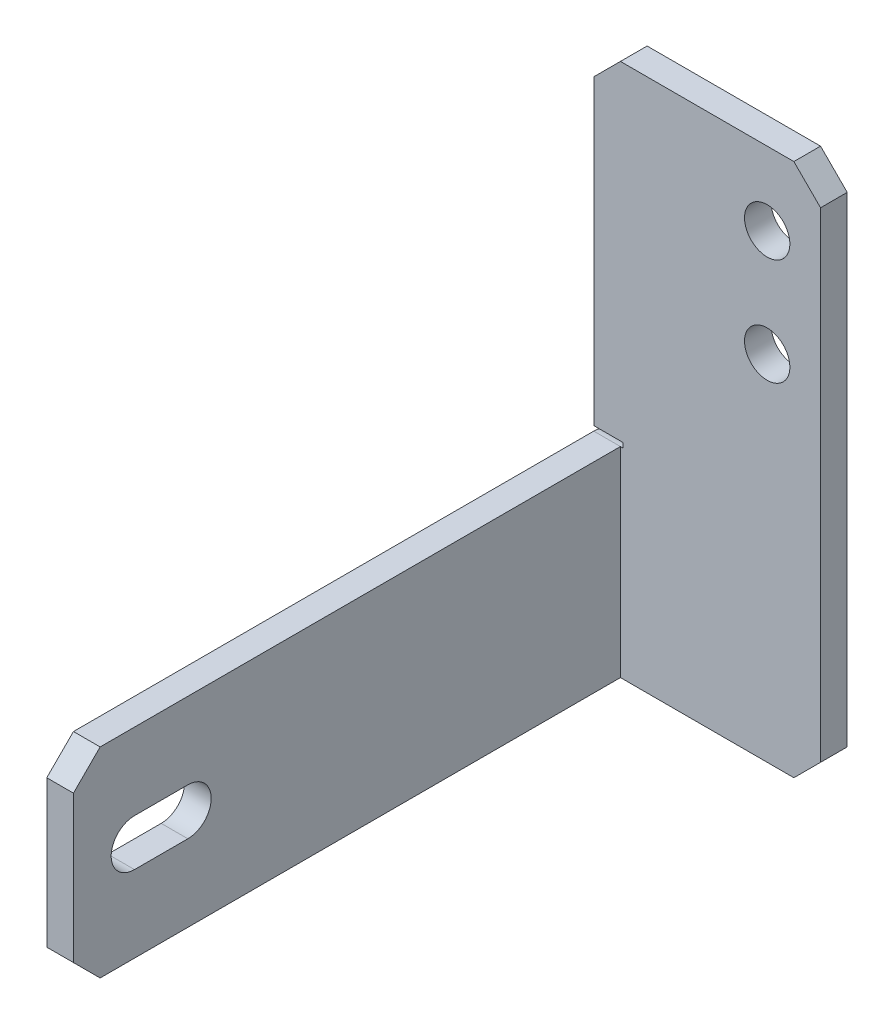
SolidWorks part; units mm, degrees
ref_plane "Front Plane" through (0, 0, 0) normal (0, 0, 1) x (1, 0, 0)
ref_plane "Top Plane" through (0, 0, 0) normal (0, 1, 0) x (1, 0, 0)
ref_plane "Right Plane" through (0, 0, 0) normal (1, 0, 0) x (0, 0, -1)
sketch "Sketch1" plane through (0, 0, 0) normal (0, 0, 1) x (1, 0, 0)
  line L0 (-8.0785, -9.7211) -> (-8.0785, -24.7211)
  line L1 (-8.0785, 15.2789) -> (8.9215, 15.2789)
  line L2 (-8.0785, 15.2789) -> (-8.0785, -9.3619)
  line L3 (-8.0785, -24.7211) -> (8.9215, -24.7211)
  line L4 (8.9215, 15.2789) -> (8.9215, -24.7211)
  line L5 (-8.0785, -9.3619) -> (-5.8785, -9.3619)
  line L7 (-8.0785, -9.7211) -> (-5.8785, -9.7211)
  line L8 (-5.8785, -9.3619) -> (-5.8785, -9.7211)
  circle A0 centre (4.9215, 9.7789) radius 1.7
  circle A1 centre (4.9215, 1.7789) radius 1.7
  dimension "D3" = 8
  dimension "D4" = 3.4
  dimension "D5" = 4
  dimension "D6" = 26.5
  dimension "D1" = 17
  dimension "D2" = 40
  dimension "D7" = 15
  dimension "D8" = 2.2
extrude "Boss-Extrude1" add sketch "Sketch1" along normal blind 2
sketch "Sketch2" plane through (0, 0, 2) normal (0, 0, 1) x (1, 0, 0)
  line L0 (-8.0785, 15.2789) -> (-8.0785, -9.3619) construction
  line L1 (-8.0785, -9.7211) -> (-6.0785, -9.7211)
  line L2 (-8.0785, -9.7211) -> (-8.0785, -24.7211)
  line L3 (-8.0785, -24.7211) -> (-6.0785, -24.7211)
  line L4 (-6.0785, -9.7211) -> (-6.0785, -24.7211)
  line L5 (-8.0785, -24.7211) -> (8.9215, -24.7211) construction
  dimension "D1" = 2
  dimension "D2" = 15
extrude "Boss-Extrude2" add sketch "Sketch2" along normal blind 41
sketch "Sketch3" plane through (-6.0785, 0, 0) normal (1, 0, 0) x (0, 0, -1)
  line L0 (-43, -24.7211) -> (-43, -9.7211) construction
  line L1 (-38.4237, -15.4711) -> (-34.4237, -15.4711)
  line L3 (-38.4237, -18.9711) -> (-34.4237, -18.9711)
  arc A0 (-38.4237, -15.4711) -> (-38.4237, -18.9711) centre (-38.4237, -17.2211) ccw
  arc A1 (-34.4237, -18.9711) -> (-34.4237, -15.4711) centre (-34.4237, -17.2211) ccw
  point P7 (-43, -17.2211)
  dimension "D1" = 4
  dimension "D2" = 3.5
extrude "Cut-Extrude1" cut sketch "Sketch3" against normal through all
fillet "Fillet1" radius 2 1 edges at (-6.9785, -9.7211, 0)
chamfer "Chamfer1" distance 2 angle 45 5 edges at (-7.0785, -9.7211, 43) (-7.0785, -24.7211, 43) (8.9215, -24.7211, 1) (-8.0785, 15.2789, 1) (8.9215, 15.2789, 1)
